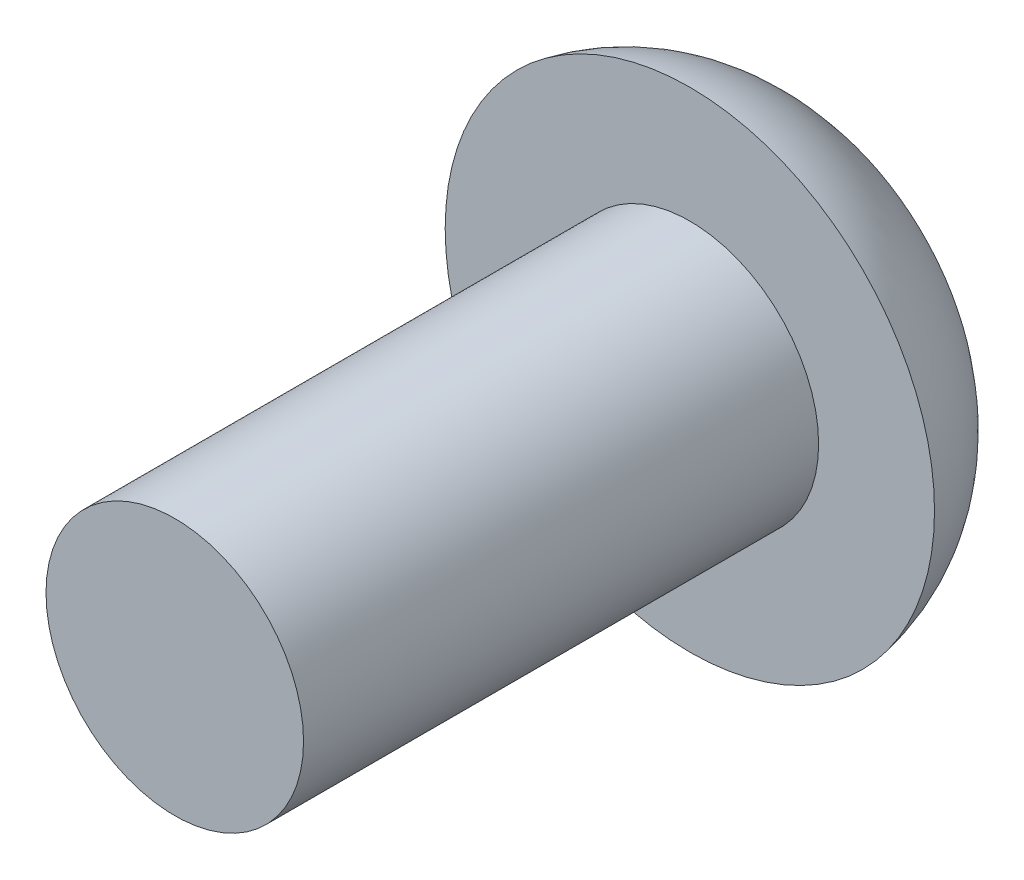
SolidWorks part; units mm, degrees
ref_plane "前视基准面" through (0, 0, 0) normal (0, 0, 1) x (1, 0, 0)
ref_plane "上视基准面" through (0, 0, 0) normal (0, 1, 0) x (1, 0, 0)
ref_plane "右视基准面" through (0, 0, 0) normal (1, 0, 0) x (0, 0, -1)
sketch "草图1" plane through (0, 0, 0) normal (0, 0, 1) x (1, 0, 0)
  circle A0 centre (0, 0) radius 1.5
extrude "凸台-拉伸1" add sketch "草图1" along normal blind 6
sketch "草图2" plane through (0, 0, 0) normal (0, 0, -1) x (-1, 0, 0)
  circle A0 centre (0, 0) radius 2.85
extrude "凸台-拉伸2" add sketch "草图2" along normal blind 1.65
fillet "圆角1" radius 2 1 edges at (-2.85, 0, -1.65)
